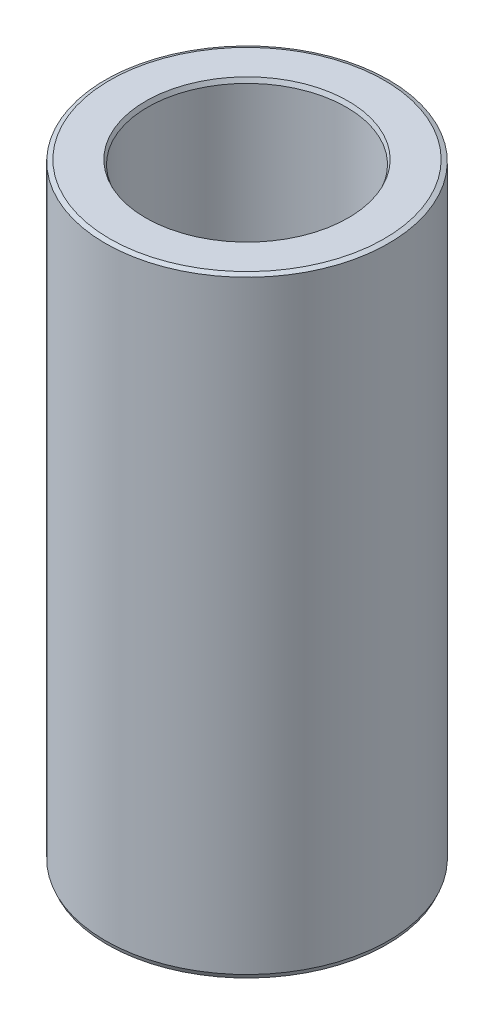
SolidWorks part; units mm, degrees
ref_plane "Front Plane" through (0, 0, 0) normal (0, 0, 1) x (1, 0, 0)
ref_plane "Top Plane" through (0, 0, 0) normal (0, 1, 0) x (1, 0, 0)
ref_plane "Right Plane" through (0, 0, 0) normal (1, 0, 0) x (0, 0, -1)
sketch "Sketch1" plane through (0, 0, 0) normal (0, 1, 0) x (1, 0, 0)
  circle A0 centre (0, 0) radius 45
  dimension "SLEEVE_OD" = 90
extrude "Boss-Extrude1" add sketch "Sketch1" along normal blind 193.8043
sketch "Sketch2" plane through (0, 0, 0) normal (0, 1, 0) x (1, 0, 0)
  circle A0 centre (0, 0) radius 31.5777
  dimension "BORE_D" = 63.1554
extrude "Cut-Extrude1" cut sketch "Sketch2" along normal through all
chamfer "Chamfer1" distance 0.5884 angle 66.979 4 edges at (0, 193.8043, 31.5777) (0, 0, 31.5777) (0, 0, 45) (0, 193.8043, 45) first distance on face at (0, 193.8043, 31.5777) first distance on face at (0, 0, 31.5777) first distance on face at (0, 193.8043, 45)
